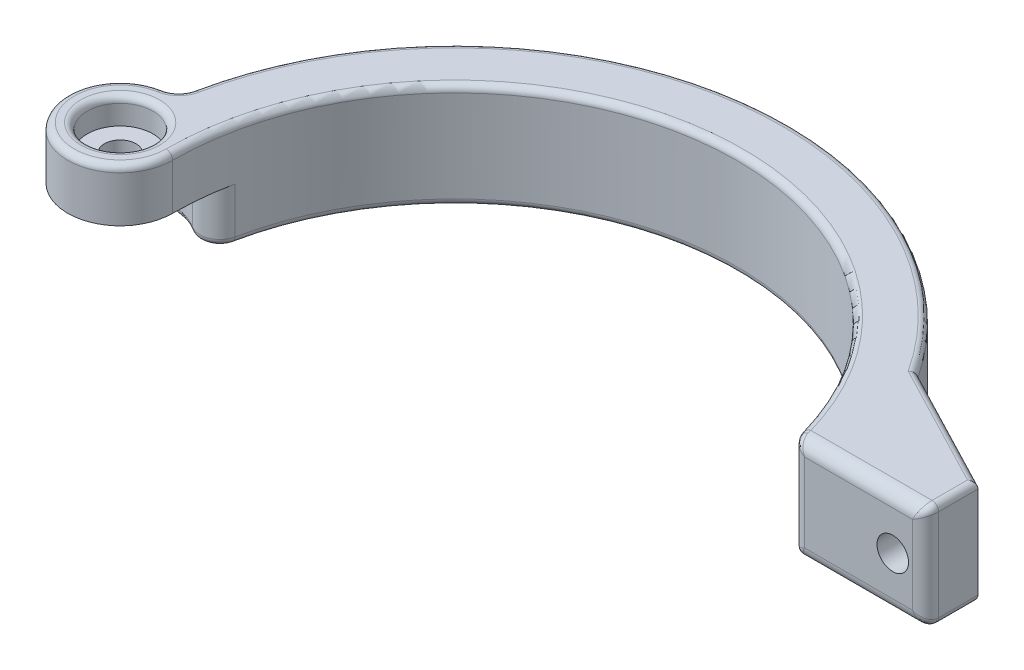
SolidWorks part; units mm, degrees
ref_plane "Front Plane" through (0, 0, 0) normal (0, 0, 1) x (1, 0, 0)
ref_plane "Top Plane" through (0, 0, 0) normal (0, 1, 0) x (1, 0, 0)
ref_plane "Right Plane" through (0, 0, 0) normal (1, 0, 0) x (0, 0, -1)
sketch "Sketch1" plane through (0, 0, 0) normal (0, 0, 1) x (1, 0, 0)
  line L0 (0, 0) -> (0, 16) construction
  line L1 (43, 0) -> (43, 16)
  line L2 (43, 16) -> (51, 16)
  line L3 (51, 16) -> (51, 0)
  line L4 (51, 0) -> (43, 0)
  point P7 (0, 0)
  dimension "D1" = 86
  dimension "D2" = 16
  dimension "D3" = 8
revolve "body" add sketch "Sketch1" angle 180 about L0
sketch "Sketch2" plane through (0, 16, 0) normal (0, 1, 0) x (1, 0, 0)
  circle A0 centre (-51, 0) radius 8
  point P2 (0, 0)
extrude "bearing_body" add sketch "Sketch2" against normal blind 8
sketch "Sketch3" plane through (0, 8, 0) normal (0, -1, 0) x (1, 0, 0)
  circle A0 centre (-51, 0) radius 8
  arc A1 (-43, 0) -> (-50.3725, -7.9754) centre (-51, 0) ccw construction
extrude "bearing_cutout" cut sketch "Sketch3" along normal through all
fillet "bearing_fillets" radius 3 2 edges at (-50.3725, 12, -7.9754) (-43, 4, 0)
sketch "Sketch4" plane through (0, 0, 0) normal (0, -1, 0) x (1, 0, 0)
  line L1 (51, 0) -> (41.821, 0)
  line L2 (51, 0) -> (51, -10)
  line L3 (51, -10) -> (41.821, -10)
  line L4 (41.821, 0) -> (41.821, -10)
  arc A0 (-50.3725, -7.9754) -> (51, 0) centre (0, 0) ccw construction
  arc A1 (-42.1202, -8.6538) -> (43, 0) centre (0, 0) ccw construction
  dimension "D1" = 10
extrude "tightening_cutout" cut sketch "Sketch4" against normal through all
sketch "Sketch5" plane through (0, 0, 0) normal (0, -1, 0) x (1, 0, 0)
  line L0 (41.821, -10) -> (61.821, -10)
  line L2 (42.6263, -28) -> (41.821, -10)
  line L3 (61.821, -10) -> (61.821, -18)
  line L4 (61.821, -18) -> (42.6263, -28)
  arc A0 (-50.3725, -7.9754) -> (50.01, -10) centre (0, 0) ccw construction
  dimension "D1" = 20
  dimension "D2" = 8
  dimension "D3" = 10
extrude "tightening_body" add sketch "Sketch5" against normal up to vertex (16 mm away) up to point (50.01, 16, -10)
ref_plane "tightening_screw_hole_plane" through (0, 0, -28) normal (0, 0, 1) x (1, 0, 0)
sketch "Sketch6" plane through (0, 0, -28) normal (0, 0, 1) x (1, 0, 0)
  line L0 (41.821, 0) -> (61.821, 0) construction
  line L1 (61.821, 16) -> (61.821, 0) construction
  point P0 (56.821, 8)
  point P1 (0, 0)
  dimension "D1" = 8
  dimension "D2" = 5
hole_wizard "tightening_screw_hole" positions "Sketch6" profile "Sketch7" counterbore size "M4" standard "DIN" end condition through all
sketch "Sketch7" plane through (56.821, 8, -28) normal (1, 0, 0) x (0, 1, 0)
  line L0 (0, 0) -> (0, 36)
  line L1 (0, 36) -> (2.4, 36)
  line L3 (2.4, 36) -> (2.4, 9)
  line L4 (2.4, 9) -> (5, 9)
  line L5 (5, 9) -> (5, 0)
  line L7 (5, 0) -> (0, 0)
  line L11 (0, -6.35) -> (0, 107.95) construction
  dimension "Thru Hole Dia." = 4.8
  dimension "Thru Hole Depth" = 36
  dimension "C'Bore Dia." = 10
  dimension "C'Bore Depth" = 9
sketch "Sketch8" plane through (0, 16, 0) normal (0, 1, 0) x (1, 0, 0)
  point P0 (-51, 0)
hole_wizard "bearing_screw_hole" positions "Sketch8" profile "Sketch9" counterbore size "M4" standard "DIN" end condition through all
sketch "Sketch9" plane through (-51, 16, 0) normal (1, 0, 0) x (0, 0, 1)
  line L0 (0, 0) -> (0, 16)
  line L1 (0, 16) -> (2.4, 16)
  line L3 (2.4, 16) -> (2.4, 4)
  line L4 (2.4, 4) -> (5, 4)
  line L5 (5, 4) -> (5, 0)
  line L7 (5, 0) -> (0, 0)
  line L11 (0, -6.35) -> (0, 107.95) construction
  dimension "Thru Hole Dia." = 4.8
  dimension "Thru Hole Depth" = 16
  dimension "C'Bore Dia." = 10
  dimension "C'Bore Depth" = 4
fillet "tightening_block_fillets" radius 2 4 edges at (41.821, 8, -10) (51.821, 0, -10) (61.821, 8, -10) (51.821, 16, -10)
fillet "general_fillets" radius 1 19 edges at (61.2353, 15.4142, -10.5858) (42.1594, 15.2111, -10.4084) (42.1594, 0.7889, -10.4084) (61.2353, 0.5858, -10.5858) (-56.1446, 16, 6.1264) (-50.8108, 16, -8.6833) (-9.6114, 16, -50.0861) (52.2237, 16, -23) (61.821, 16, -15) (-6.0605, 16, -42.5708) (-51, 16, 5) (52.2237, 0, -23) (-10.7354, 0, -49.8573) (-48.449, 0, -7.5824) (-43.8939, 0, -6.493) (-1.7236, 0, -42.9654) (61.821, 0, -15)
equation "\"paper_size\" = 600mm"
equation "\"cb_roll_d_outer\" = 86mm"
equation "\"cb_roll_d_inner\" = 76mm"
equation "\"helper_d\" = 92mm"
equation "\"outer_d\" = 112mm"
equation "\"spring_l_max\" = 25mm"
equation "\"spring_l_min\" = 10mm"
equation "\"attached_len\" = \"spring_l_max\" * 2 - \"spring_l_min\" + 18"
equation "\"cone_d_larger\" = 40mm"
equation "\"cone_angle\" = 60deg"
equation "\"bottom_screw_ring_d\" = 92mm"
equation "\"D1@Sketch1\"=\"cb_roll_d_outer\""
